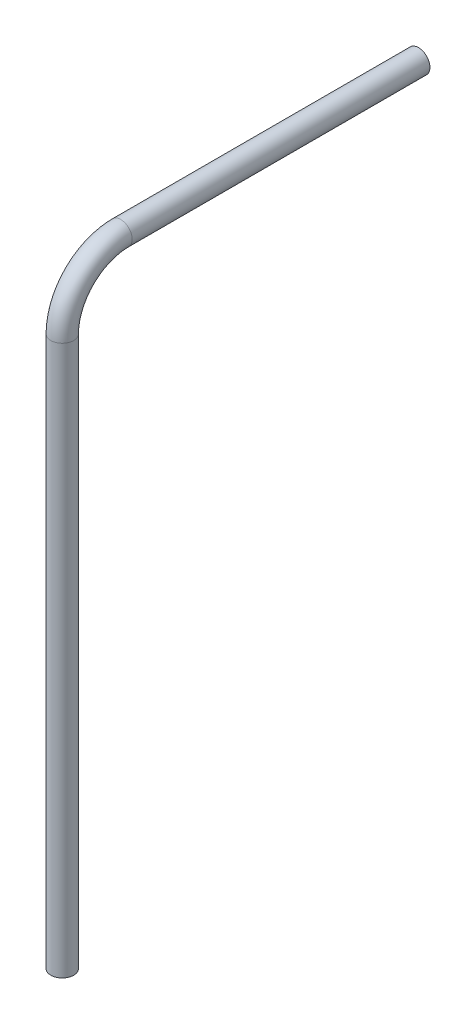
SolidWorks part; units mm, degrees
material "Cast Carbon Steel"
ref_plane "Front Plane" through (0, 0, 0) normal (0, 0, 1) x (1, 0, 0)
ref_plane "Top Plane" through (0, 0, 0) normal (0, 1, 0) x (1, 0, 0)
ref_plane "Right Plane" through (0, 0, 0) normal (1, 0, 0) x (0, 0, -1)
sketch "Sketch2" plane through (0, 0, 0) normal (1, 0, 0) x (0, 0, -1)
  arc A0 (-64.8338, 0) -> (0, 64.8338) centre (0, 0) cw
sketch "Sketch3" plane through (0, 0, 0) normal (0, 1, 0) x (1, 0, 0)
  circle A0 centre (0, -64.8338) radius 12.7
  circle A1 centre (0, -64.8338) radius 4.7625
  dimension "D1" = 25.4
  dimension "D2" = 7.9375
sweep "Sweep1" add profiles "Sketch3" path "Sketch2"
ref_plane "Plane1" through (0, 0, 0) normal (0, -1, 0) x (-1, 0, 0)
ref_plane "Plane2" through (0, 0, 0) normal (0, 0, -1) x (-1, 0, 0)
sketch "Sketch4" plane through (0, 0, 0) normal (0, -1, 0) x (-1, 0, 0)
  circle A0 centre (0, -64.8338) radius 12.7
  circle A1 centre (0, -64.8338) radius 4.7625
  dimension "D1" = 7.9375
  dimension "D2" = 25.4
extrude "Boss-Extrude3" add sketch "Sketch4" along normal blind 609.6
sketch "Sketch5" plane through (0, 0, 0) normal (0, 0, -1) x (-1, 0, 0)
  circle A2 centre (0, 64.8338) radius 4.7625
  circle A3 centre (0, 64.8338) radius 12.7
  circle A5 centre (0, 64.8338) radius 12.7 construction
  dimension "D2" = 25.4
extrude "Boss-Extrude4" add sketch "Sketch5" along normal blind 330.2
ref_plane "Plane3" through (-12.7, 0, 0) normal (-1, 0, 0) x (0, 0, 1)
sketch "Sketch6" plane through (-12.7, 0, 0) normal (-1, 0, 0) x (0, 0, 1)
  line L0 (52.1338, 0) -> (77.5338, 0) construction
  line L1 (57.15, -152.4) -> (69.85, -152.4)
  line L2 (57.15, -152.4) -> (57.15, 0)
  line L3 (57.15, 0) -> (69.85, 0)
  line L4 (69.85, -152.4) -> (69.85, 0)
  point P12 (63.5, -152.4)
  point P13 (63.5, -152.4)
  dimension "D1" = 57.15
  dimension "D2" = 63.5
  dimension "D3" = 152.4
extrude "Cut-Extrude1" cut sketch "Sketch6" against normal blind 6.35
